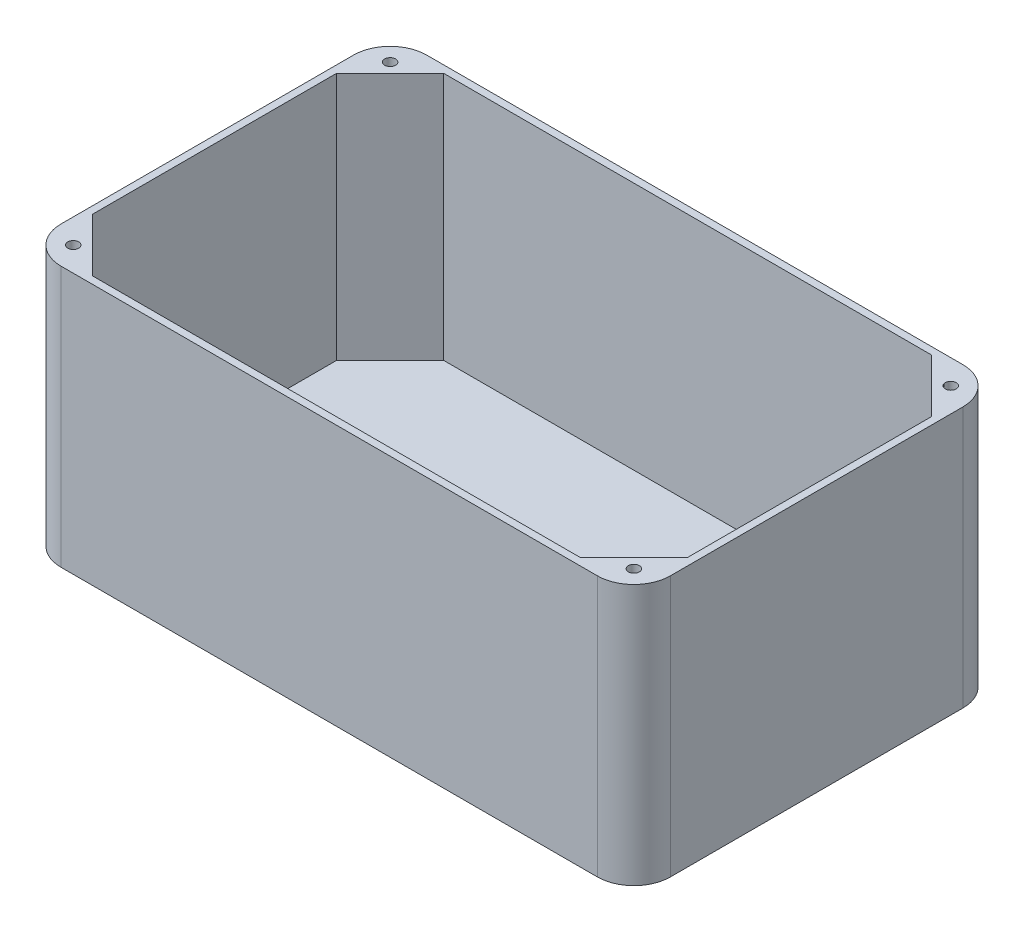
SolidWorks part; units mm, degrees
material "ABS"
ref_plane "Alzado" through (0, 0, 0) normal (0, 0, 1) x (1, 0, 0)
ref_plane "Planta" through (0, 0, 0) normal (0, 1, 0) x (1, 0, 0)
ref_plane "Vista lateral" through (0, 0, 0) normal (1, 0, 0) x (0, 0, -1)
sketch "Croquis1" plane through (0, 0, 0) normal (0, 1, 0) x (1, 0, 0)
  line L1 (-125, -75) -> (125, -75)
  line L2 (-125, -75) -> (-125, 75)
  line L3 (-125, 75) -> (125, 75)
  line L4 (125, -75) -> (125, 75)
  line L5 (-125, -75) -> (125, 75) construction
  line L6 (-125, 75) -> (125, -75) construction
  point P0 (0, 0)
  dimension "D1" = 250
  dimension "D2" = 150
extrude "Saliente-Extruir1" add sketch "Croquis1" along normal blind 110
fillet "Redondeo1" radius 15 4 edges at (-125, 55, -75) (125, 55, -75) (125, 55, 75) (-125, 55, 75)
shell "Vaciado2" thickness 3 removed face at (0, 0, 0)
sketch "Croquis3" plane through (0, 0, 0) normal (0, -1, 0) x (1, 0, 0)
  line L1 (-125, -75) -> (125, -75)
  line L2 (-125, -75) -> (-125, 75)
  line L3 (-125, 75) -> (125, 75)
  line L4 (125, -75) -> (125, 75)
  line L5 (-125, -75) -> (125, 75) construction
  line L6 (-125, 75) -> (125, -75) construction
  point P0 (0, 0)
extrude "Saliente-Extruir2" add sketch "Croquis3" against normal blind 5
fillet "Redondeo2" radius 15 4 edges at (125, 2.5, 75) (125, 2.5, -75) (-125, 2.5, -75) (-125, 2.5, 75)
sketch "Croquis4" plane through (0, 110, 0) normal (0, 1, 0) x (1, 0, 0)
  line L1 (-125, -75) -> (125, -75)
  line L2 (-125, -75) -> (-125, 75)
  line L3 (-125, 75) -> (125, 75)
  line L4 (125, -75) -> (125, 75)
  line L5 (-125, -75) -> (125, 75) construction
  line L6 (-125, 75) -> (125, -75) construction
  point P0 (0, 0)
extrude "Cortar-Extruir1" cut sketch "Croquis4" against normal blind 3
sketch "Croquis5" plane through (0, 107, 0) normal (0, 1, 0) x (1, 0, 0)
  line L0 (-122, 60) -> (-122, 50)
  line L1 (-125, -75) -> (-97, -75)
  line L2 (-125, -75) -> (-125, -47)
  line L3 (-125, 75) -> (-97, 75)
  line L4 (125, -75) -> (125, -47)
  line L5 (-125, -75) -> (-107.5, -64.5) construction
  line L6 (-125, 75) -> (-107.5, 64.5) construction
  line L7 (-122, 60) -> (-122, -60) construction
  line L8 (-122, 50) -> (-100, 72)
  line L9 (110, 72) -> (-110, 72) construction
  line L10 (-100, 72) -> (-110, 72)
  line L11 (-122, 50) -> (-125, 47)
  line L12 (-100, 72) -> (-97, 75)
  line L13 (0, 75) -> (0, 0) construction
  line L15 (100, 72) -> (97, 75)
  line L16 (122, 50) -> (125, 47)
  line L17 (122, 50) -> (100, 72)
  line L18 (-122, -50) -> (-125, -47)
  line L19 (-100, -72) -> (-97, -75)
  line L20 (100, -72) -> (97, -75)
  line L21 (122, -50) -> (125, -47)
  line L22 (122, -50) -> (100, -72)
  line L23 (-122, -50) -> (-100, -72)
  line L24 (125, 47) -> (125, 75)
  line L25 (97, 75) -> (125, 75)
  line L26 (107.5, -64.5) -> (125, -75) construction
  line L27 (97, -75) -> (125, -75)
  line L28 (107.5, 64.5) -> (125, 75) construction
  line L29 (-125, 47) -> (-125, 75)
  arc A0 (-110, 72) -> (-122, 60) centre (-110, 60) ccw construction
  point P0 (0, 0)
  arc M3 (-110, 75) -> (-125, 60) centre (-110, 60) ccw
  line M4 (-125, 60) -> (-125, -60)
  line M6 (-110, -75) -> (110, -75)
  arc M7 (110, -75) -> (125, -60) centre (110, -60) ccw
  line M8 (125, -60) -> (125, 60)
  line M10 (110, 75) -> (-110, 75)
  arc M11 (110, 72) -> (122, 60) centre (110, 60) cw
  line M12 (122, 60) -> (122, -60)
  arc M13 (122, -60) -> (110, -72) centre (110, -60) cw
  line M14 (110, -72) -> (-110, -72)
  line M16 (-122, -60) -> (-122, 60)
  arc M17 (-122, 60) -> (-110, 72) centre (-110, 60) cw
  line M18 (-110, 72) -> (110, 72)
  dimension "D1" = 10
  dimension "D2" = 10
extrude "Saliente-Extruir3" add sketch "Croquis5" against normal up to surface (107 mm away) contours L8 M16 M18 M17 | L29 L3 M3 | L12 L11 M18 M10 M3 M4 M16 M17 | L22 M12 M14 M13 | L27 L4 M7 | L21 L20 M12 M13 M14 M6 M7 M8 | L17 M12 M11 M18 | L25 L24 L16 L17 L15 | L2 L18 L23 L19 L1 region at (-113.9855, 107, -63.9855) region at (-122.396, 107, -55) region at (113.9855, 107, -63.9855) region at (-121.6495, 107, -71.6495) region at (105, 107, 72.396) region at (113.9855, 107, 63.9855) region at (121.6495, 107, 71.6495) up to face at (0, 0, 0)
fillet "Redondeo3" radius 15 4 edges at (125, 53.5, -75) (125, 53.5, 75) (-125, 53.5, 75) (-125, 53.5, -75)
sketch "Croquis6" plane through (0, 107, 0) normal (0, 1, 0) x (1, 0, 0)
  line L0 (110, 75) -> (-110, 75) construction
  line L1 (-125, 60) -> (-125, -60) construction
  line L2 (0, 110.9924) -> (0, -102.0227) construction
  line L3 (-157.9674, 0) -> (173.2737, 0) construction
  circle A0 centre (-115, 65) radius 3.1357
  circle A1 centre (115, 65) radius 3.1357
  circle A2 centre (115, -65) radius 3.1357
  circle A3 centre (-115, -65) radius 3.1357
  point P0 (-115, 65)
  point P11 (115, 65)
  point P13 (115, -65)
  point P15 (-115, -65)
  dimension "D1" = 10
  dimension "D2" = 10
hole_wizard "Taladro de margen para M41" positions "Croquis6" profile "Croquis7" hole size "M4" standard "GB"
sketch "Croquis7" plane through (-115, 107, -65) normal (1, 0, 0) x (0, 0, 1)
  line L0 (0, 0) -> (0, 41.3519)
  line L1 (0, 41.3519) -> (2.25, 40)
  line L2 (2.25, 40) -> (2.25, 0)
  line L5 (2.25, 0) -> (0, 0)
  line L10 (0, 41.3519) -> (-2.25, 40) construction
  line L11 (0, -6.35) -> (0, 107.95) construction
  dimension "Di醡etro de taladro" = 4.5
  dimension "Profundidad de taladro" = 40
  dimension "羘gulo de perforador" = 118
